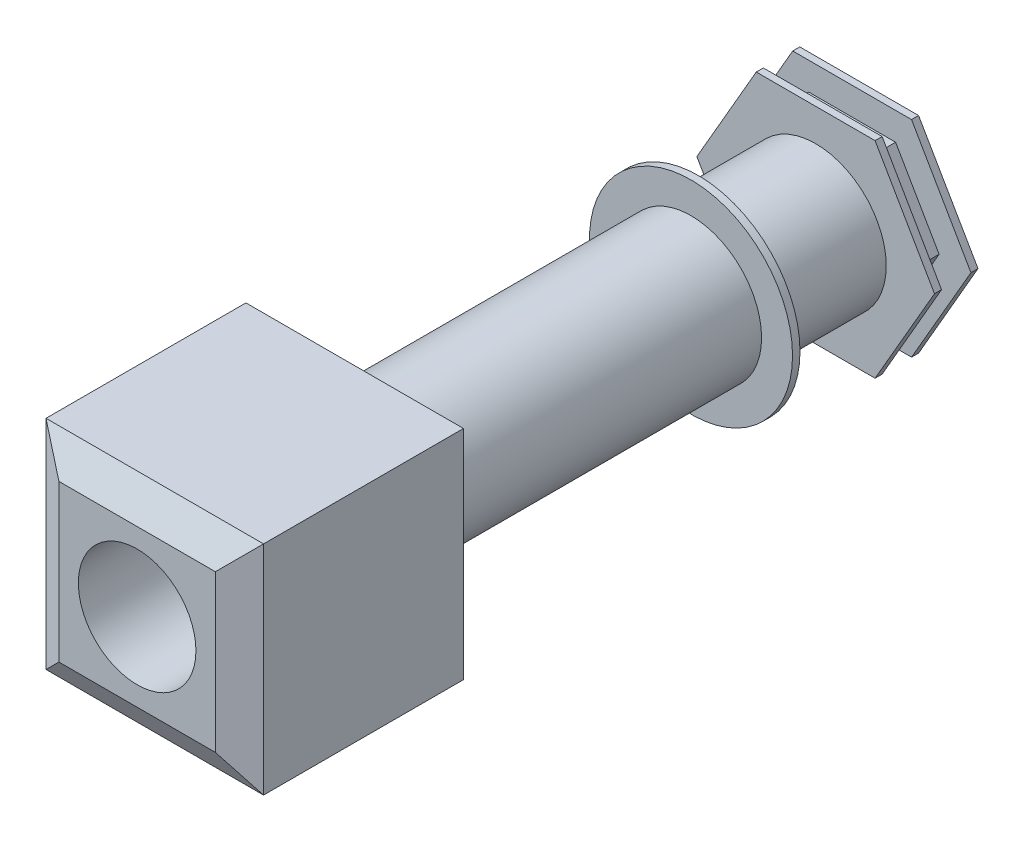
SolidWorks part; units mm, degrees
ref_plane "Front Plane" through (0, 0, 0) normal (0, 0, 1) x (1, 0, 0)
ref_plane "Top Plane" through (0, 0, 0) normal (0, 1, 0) x (1, 0, 0)
ref_plane "Right Plane" through (0, 0, 0) normal (1, 0, 0) x (0, 0, -1)
sketch "Sketch1" plane through (0, 0, 0) normal (0, 0, 1) x (1, 0, 0)
  line L1 (202.0726, 0) -> (101.0363, 175)
  line L2 (101.0363, 175) -> (-101.0363, 175)
  line L3 (-101.0363, 175) -> (-202.0726, 0)
  line L4 (-202.0726, 0) -> (-101.0363, -175)
  line L5 (-101.0363, -175) -> (101.0363, -175)
  line L6 (101.0363, -175) -> (202.0726, 0)
  circle A0 centre (0, 0) radius 175 construction
extrude "Boss-Extrude1" add sketch "Sketch1" along normal blind 12
sketch "Sketch2" plane through (0, 0, 12) normal (0, 0, 1) x (1, 0, 0)
  line L1 (147.8875, 0) -> (73.9437, 128.0743)
  line L2 (73.9437, 128.0743) -> (-73.9437, 128.0743)
  line L3 (-73.9437, 128.0743) -> (-147.8875, 0)
  line L4 (-147.8875, 0) -> (-73.9437, -128.0743)
  line L5 (-73.9437, -128.0743) -> (73.9437, -128.0743)
  line L6 (73.9437, -128.0743) -> (147.8875, 0)
  circle A0 centre (0, 0) radius 128.0743 construction
extrude "Boss-Extrude2" add sketch "Sketch2" along normal blind 50
sketch "Sketch3" plane through (0, 0, 62) normal (0, 0, 1) x (1, 0, 0)
  line L1 (202.0726, 0) -> (101.0363, 175)
  line L2 (101.0363, 175) -> (-101.0363, 175)
  line L3 (-101.0363, 175) -> (-202.0726, 0)
  line L4 (-202.0726, 0) -> (-101.0363, -175)
  line L5 (-101.0363, -175) -> (101.0363, -175)
  line L6 (101.0363, -175) -> (202.0726, 0)
  circle A0 centre (0, 0) radius 175 construction
extrude "Boss-Extrude3" add sketch "Sketch3" along normal blind 12
sketch "Sketch4" plane through (0, 0, 74) normal (0, 0, 1) x (1, 0, 0)
  circle A0 centre (0, 0) radius 120
extrude "Boss-Extrude4" add sketch "Sketch4" along normal blind 200
sketch "Sketch5" plane through (0, 0, 274) normal (0, 0, 1) x (1, 0, 0)
  circle A0 centre (0, 0) radius 172.6469
extrude "Boss-Extrude5" add sketch "Sketch5" along normal blind 12
chamfer "Chamfer1" distance 10 angle 80 1 edges at (120, 0, 274) first distance on face at (120, 0, 274)
sketch "Sketch6" plane through (0, 0, 286) normal (0, 0, 1) x (1, 0, 0)
  circle A0 centre (0, 0) radius 120
extrude "Boss-Extrude6" add sketch "Sketch6" along normal blind 560
sketch "Sketch8" plane through (0, 0, 846) normal (0, 0, 1) x (1, 0, 0)
  circle A0 centre (0, 0) radius 172.6469
extrude "Boss-Extrude7" add sketch "Sketch8" along normal blind 12
chamfer "Chamfer2" distance 6 angle 70 1 edges at (120, 0, 846) first distance on face at (120, 0, 846)
sketch "Sketch9" plane through (0, 0, 858) normal (0, 0, 1) x (1, 0, 0)
  line L1 (-185, 185) -> (185, 185)
  line L2 (-185, 185) -> (-185, -185)
  line L3 (-185, -185) -> (185, -185)
  line L4 (185, 185) -> (185, -185)
  line L5 (-185, 185) -> (185, -185) construction
  line L6 (-185, -185) -> (185, 185) construction
  point P0 (0, 0)
extrude "Boss-Extrude8" add sketch "Sketch9" along normal blind 370
sketch "Sketch10" plane through (0, 0, 1228) normal (0, 0, 1) x (1, 0, 0)
  circle A0 centre (0, 0) radius 100
extrude "Cut-Extrude1" cut sketch "Sketch10" against normal blind 900
chamfer "Chamfer3" distance 30 angle 60 4 edges at (185, 0, 1228) (0, -185, 1228) (-185, 0, 1228) (0, 185, 1228) first distance on face at (185, 0, 1043) first distance on face at (0, -185, 1043) first distance on face at (-185, 0, 1043) first distance on face at (0, 185, 1043)
